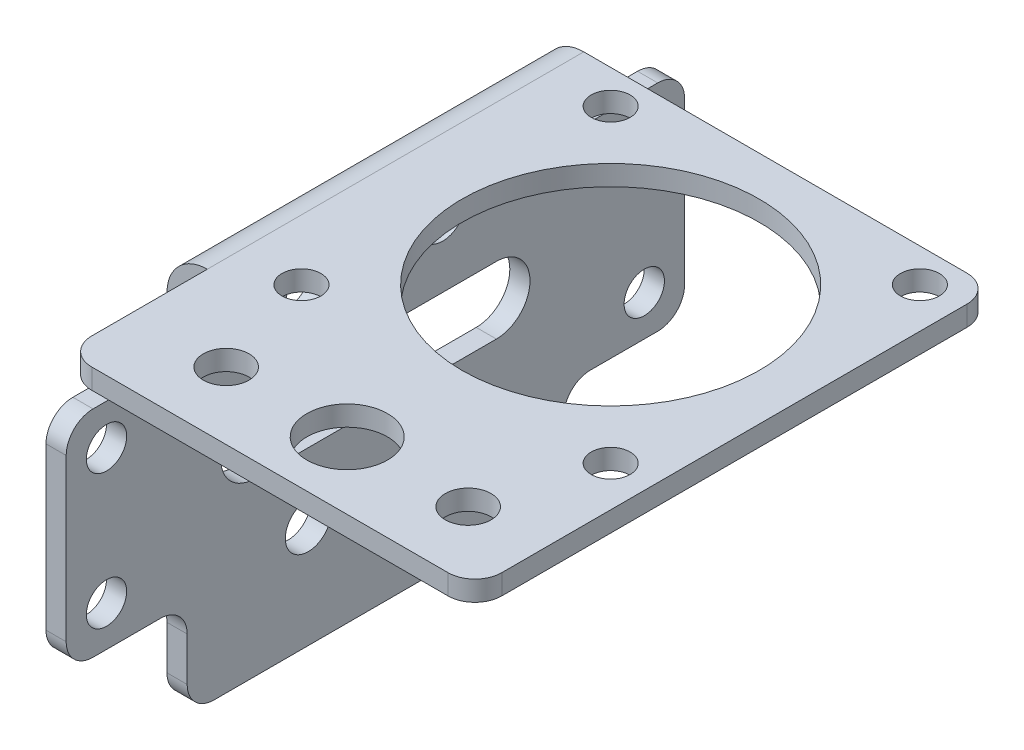
SolidWorks part; units mm, degrees
note: The reader was unsure of these and kept them because the rebuilt part matched: bend radius of "BaseBend1".
material "Plain Carbon Steel"
ref_plane "Front Plane" through (0, 0, 0) normal (0, 0, 1) x (1, 0, 0)
ref_plane "Top Plane" through (0, 0, 0) normal (0, 1, 0) x (1, 0, 0)
ref_plane "Right Plane" through (0, 0, 0) normal (1, 0, 0) x (0, 0, -1)
sketch "Sketch1" plane through (0, 0, 0) normal (0, 0, 1) x (1, 0, 0)
  line L0 (0, -24) -> (0, 0)
  line L1 (0, 0) -> (32, 0)
  dimension "D1" = 32
  dimension "D2" = 24
base flange "Base-Flange1" sketch "Sketch1" end condition mid plane depth 28 reverse direction no thickness 1.5 reverse thickness direction yes bend radius 1.5
bend "BaseBend1" bend radius 1.5 bend angle 90 parameters "D5"=1
hole_wizard "M3 Clearance Hole1" positions "Sketch6" profile "Sketch7" hole size "M3" standard "ISO" end condition through all
sketch "Sketch6" plane through (-1.5, 0, 0) normal (-1, 0, 0) x (0, 0, 1)
  line L0 (-5, -5.25) -> (-5, -20.25) construction
  line L1 (5, -5.25) -> (5, -20.25) construction
  line L2 (5, -20.25) -> (-5, -20.25) construction
  line L4 (0, -20.25) -> (0, -24) construction
  line L5 (14, -24) -> (-14, -24) construction
  line L7 (-5, -12.75) -> (-14, -12.75) construction
  line L8 (-14, -24) -> (-14, -1.5) construction
  point P0 (-5, -5.25)
  point P2 (-5, -20.25)
  point P11 (5, -5.25)
  point P13 (5, -20.25)
  dimension "D1" = 15
  dimension "D2" = 10
sketch "Sketch7" plane through (-1.5, -5.25, -5) normal (0, 1, 0) x (0, 0, 1)
  line L0 (0, 0) -> (0, 33.5)
  line L1 (0, 33.5) -> (1.7, 33.5)
  line L2 (1.7, 33.5) -> (1.7, 0)
  line L5 (1.7, 0) -> (0, 0)
  line L11 (0, -6.35) -> (0, 107.95) construction
  dimension "Thru Hole Dia." = 3.4
  dimension "Thru Hole Depth" = 33.5
hole_wizard "M2.5 Clearance Hole1" positions "Sketch8" profile "Sketch9" hole size "M2.5" standard "ISO" end condition through all
sketch "Sketch8" plane through (0, 1.5, 0) normal (0, 1, 0) x (1, 0, 0)
  line L0 (6, -11.5) -> (29, -11.5) construction
  line L1 (29, -11.5) -> (29, 11.5) construction
  line L2 (29, 11.5) -> (6, 11.5) construction
  line L4 (29, 0) -> (32, 0) construction
  line L5 (32, -14) -> (32, 14) construction
  point P0 (29, 11.5)
  point P2 (29, -11.5)
  point P4 (6, -11.5)
  point P6 (6, 11.5)
  dimension "D1" = 23
  dimension "D2" = 3
sketch "Sketch9" plane through (29, 1.5, -11.5) normal (1, 0, 0) x (0, 0, 1)
  line L0 (0, 0) -> (0, 25.5)
  line L1 (0, 25.5) -> (1.45, 25.5)
  line L2 (1.45, 25.5) -> (1.45, 0)
  line L5 (1.45, 0) -> (0, 0)
  line L11 (0, -6.35) -> (0, 107.95) construction
  dimension "Thru Hole Dia." = 2.9
  dimension "Thru Hole Depth" = 25.5
sketch "Sketch10" plane through (0, 1.5, 0) normal (0, 1, 0) x (1, 0, 0)
  line L0 (29, 11.5) -> (29, -11.5) construction
  line L1 (6, -11.5) -> (29, -11.5) construction
  line L2 (17.5, -11.5) -> (17.5, 0) construction
  line L3 (17.5, 0) -> (29, 0) construction
  circle A0 centre (17.5, 0) radius 11.05
  dimension "D1" = 22.1
extrude "Cut-Extrude1" cut sketch "Sketch10" against normal blind 10
sketch "Sketch11" plane through (0, 1.5, 0) normal (0, 1, 0) x (1, 0, 0)
  line L2 (32, -14) -> (1.5, -14)
  line L3 (17.5, -14) -> (17.5, -24.597) construction
  line L4 (1.5, -14) -> (1.5, -24.597)
  line L7 (17.5, 0) -> (17.5, -14) construction
  line L10 (1.5, -24.597) -> (17.5, -24.597)
  line L11 (17.5, -24.597) -> (32, -24.597)
  line L12 (32, -24.597) -> (32, -14)
  line L13 (28, -24.597) -> (7, -24.597) construction
  circle A8 centre (17.5, -19.597) radius 3
  dimension "D4" = 6
extrude "Boss-Extrude1" add sketch "Sketch11" against normal blind 1.5
hole_wizard "M3 Clearance Hole2" positions "Sketch12" profile "Sketch13" hole size "M3" standard "ISO" end condition through all
sketch "Sketch12" plane through (0, 0, 0) normal (0, -1, 0) x (-1, 0, 0)
  point P0 (-26.5, -19.597)
  point P3 (-8.5, -19.597)
sketch "Sketch13" plane through (26.5, 0, 19.597) normal (1, 0, 0) x (0, 0, -1)
  line L0 (0, 0) -> (0, 1.5)
  line L1 (0, 1.5) -> (1.7, 1.5)
  line L2 (1.7, 1.5) -> (1.7, 0)
  line L5 (1.7, 0) -> (0, 0)
  line L11 (0, -6.35) -> (0, 107.95) construction
  dimension "Thru Hole Dia." = 3.4
  dimension "Thru Hole Depth" = 1.5
sketch "Sketch14" plane through (0, 0, 0) normal (1, 0, 0) x (0, 0, -1)
  line L0 (14, -4.75) -> (23, -4.75)
  line L1 (14, -24) -> (14, -1.5) construction
  line L2 (23, -4.75) -> (23, -20.75)
  line L3 (23, -20.75) -> (14, -20.75)
  line L4 (14, -20.75) -> (14, -4.75)
  line L5 (14, -9.75) -> (23, -9.75) construction
  line L6 (23, -15.75) -> (14, -15.75) construction
  line L7 (20, -9.75) -> (20, -15.75) construction
  line L8 (20, -12.75) -> (23, -12.75) construction
  line L9 (20, -7.75) -> (20, -9.75) construction
  line L10 (20, -17.75) -> (20, -15.75) construction
  line L11 (-14, -24) -> (14, -24) construction
  circle A0 centre (20, -7.75) radius 1.5
  circle A1 centre (20, -17.75) radius 1.5
  dimension "D4" = 3
  dimension "D1" = 9
  dimension "D2" = 6
  dimension "D3" = 2
  dimension "D5" = 3
  dimension "D6" = 2
  dimension "D7" = 11.25
  dimension "D8" = 16
extrude "Boss-Extrude2" add sketch "Sketch14" against normal blind 1.5
mirror "Mirror1" about plane through (0, 0, 0) normal (0, 0, 1) of "Boss-Extrude2"
sketch "Sketch15" plane through (0, 0, 0) normal (1, 0, 0) x (0, 0, -1)
  line L1 (-14, -24) -> (14, -24)
  line L2 (-14, -24) -> (-14, -28)
  line L3 (-14, -28) -> (14, -28)
  line L4 (14, -24) -> (14, -28)
  dimension "D1" = 4
extrude "Boss-Extrude3" add sketch "Sketch15" against normal blind 1.5
fillet "Fillet1" radius 2 13 edges at (-0.75, -20.75, -14) (-0.75, -4.75, -14) (-0.75, -4.75, -23) (-0.75, -20.75, -23) (-0.75, -4.75, 14) (-0.75, -20.75, 14) (-0.75, -20.75, 23) (-0.75, -4.75, 23) (-0.75, -28, 14) (-0.75, -28, -14) (1.5, 0.75, 24.597) (32, 0.75, 24.597) (32, 0.75, -14)
sketch "Sketch16" plane through (0, 0, 0) normal (1, 0, 0) x (0, 0, -1)
  line L0 (-9, -12.75) -> (9, -12.75) construction
  line L1 (-9, -10.25) -> (9, -10.25)
  line L2 (-9, -15.25) -> (9, -15.25)
  line L3 (0, 0) -> (0, -12.75) construction
  line L4 (-5, -5.25) -> (-5, -12.75) construction
  line L5 (-5, -12.75) -> (-5, -20.25) construction
  arc A0 (-9, -10.25) -> (-9, -15.25) centre (-9, -12.75) ccw
  arc A1 (9, -15.25) -> (9, -10.25) centre (9, -12.75) ccw
  point P2 (0, -12.75)
  dimension "D1" = 18
  dimension "D2" = 5
extrude "Cut-Extrude2" cut sketch "Sketch16" against normal blind 10
sketch "Bend-Lines1" [suppressed] plane through (0, 0, 0) normal (0, 1, 0) x (1, 0, 0)
sketch "Bounding-Box1" [suppressed] plane through (0, 0, 0) normal (0, 1, 0) x (1, 0, 0)
sheet metal parameters "Sheet-Metal1" thickness 1.5 parameters "D1"=1.5
flat pattern "Flat-Pattern1" [suppressed]
sketch "Bend-Lines2" plane through (0, 1.5, 0) normal (0, 1, 0) x (1, 0, 0)
  line L0 (-0.2671, -14) -> (-0.2671, 14) construction
  line L1 (-0.2671, -14) -> (-0.2671, 14) construction
sketch3d "Bounding-Box2" [suppressed]
  line L0 (30, 0, 0) -> (-20.5343, 0, 0) construction
  line L1 (30, 28, 0) -> (-20.5343, 28, 0) construction
  line L2 (30, 0, 0) -> (30, 28, 0) construction
  line L3 (-20.5343, 0, 0) -> (-20.5343, 28, 0) construction
bend of the flat pattern "Flatten-<BaseBend1>1"
sheet metal parameters "Sheet-Metal2" thickness 1.5 parameters "D1"=1.5
flat pattern "Flat-Pattern1"
sketch "Bend-Lines2" plane through (0, 1.5, 0) normal (0, 1, 0) x (1, 0, 0)
  line L0 (-0.2671, -14) -> (-0.2671, 14) construction
  line L1 (-0.2671, -14) -> (-0.2671, 14) construction
sketch3d "Bounding-Box2" [suppressed]
  line L0 (30, 0, 0) -> (-20.5343, 0, 0) construction
  line L1 (30, 28, 0) -> (-20.5343, 28, 0) construction
  line L2 (30, 0, 0) -> (30, 28, 0) construction
  line L3 (-20.5343, 0, 0) -> (-20.5343, 28, 0) construction
bend of the flat pattern "Flatten-<BaseBend1>1"
sheet metal parameters "Sheet-Metal3" thickness 1.5 parameters "D1"=1.5
flat pattern "Flat-Pattern1"
sketch "Bend-Lines2" plane through (0, 1.5, 0) normal (0, 1, 0) x (1, 0, 0)
  line L0 (-0.2671, -14) -> (-0.2671, 14) construction
  line L1 (-0.2671, -14) -> (-0.2671, 14) construction
sketch3d "Bounding-Box2" [suppressed]
  line L0 (32, 0, 0) -> (-20.5343, 0, 0) construction
  line L1 (32, 28, 0) -> (-20.5343, 28, 0) construction
  line L2 (32, 0, 0) -> (32, 28, 0) construction
  line L3 (-20.5343, 0, 0) -> (-20.5343, 28, 0) construction
bend of the flat pattern "Flatten-<BaseBend1>1"
sheet metal parameters "Sheet-Metal4" thickness 1.5 parameters "D1"=1.5
flat pattern "Flat-Pattern1"
sketch "Bend-Lines2" plane through (0, 1.5, 0) normal (0, 1, 0) x (1, 0, 0)
  line L0 (-0.2671, -14) -> (-0.2671, 14) construction
  line L1 (-0.2671, -14) -> (-0.2671, 14) construction
sketch3d "Bounding-Box2" [suppressed]
  line L0 (32, 0, 0) -> (-24.5343, 0, 0) construction
  line L1 (32, 28, 0) -> (-24.5343, 28, 0) construction
  line L2 (32, 0, 0) -> (32, 28, 0) construction
  line L3 (-24.5343, 0, 0) -> (-24.5343, 28, 0) construction
bend of the flat pattern "Flatten-<BaseBend1>1"
sheet metal parameters "Sheet-Metal5" thickness 1.5 parameters "D1"=1.5
flat pattern "Flat-Pattern1"
sketch "Bend-Lines2" plane through (0, 1.5, 0) normal (0, 1, 0) x (1, 0, 0)
  line L0 (-0.2671, -14) -> (-0.2671, 14) construction
  line L1 (-0.2671, -14) -> (-0.2671, 14) construction
sketch3d "Bounding-Box2" [suppressed]
  line L0 (32, 28, 0) -> (32, -28.7409, 0) construction
  line L1 (-24.5343, 28, 0) -> (-24.5343, -28.7409, 0) construction
  line L2 (32, 28, 0) -> (-24.5343, 28, 0) construction
  line L3 (32, -28.7409, 0) -> (-24.5343, -28.7409, 0) construction
bend of the flat pattern "Flatten-<BaseBend1>1"
sheet metal parameters "Sheet-Metal7" thickness 1.5 parameters "D1"=1.5
flat pattern "Flat-Pattern1"
sketch "Bend-Lines2" plane through (0, 1.5, 0) normal (0, 1, 0) x (1, 0, 0)
  line L0 (-0.2671, -14) -> (-0.2671, 14) construction
  line L1 (-0.2671, -14) -> (-0.2671, 14) construction
sketch3d "Bounding-Box2" [suppressed]
  line L0 (32, 0, 0) -> (-24.5343, 0, 0) construction
  line L1 (32, 28, 0) -> (-24.5343, 28, 0) construction
  line L2 (32, 0, 0) -> (32, 28, 0) construction
  line L3 (-24.5343, 0, 0) -> (-24.5343, 28, 0) construction
bend of the flat pattern "Flatten-<BaseBend1>1"
sheet metal parameters "Sheet-Metal8" thickness 1.5 parameters "D1"=1.5
flat pattern "Flat-Pattern1"
sketch "Bend-Lines2" plane through (0, 1.5, 0) normal (0, 1, 0) x (1, 0, 0)
  line L0 (-0.2671, -14) -> (-0.2671, 14) construction
  line L1 (-0.2671, -14) -> (-0.2671, 14) construction
sketch3d "Bounding-Box2" [suppressed]
  line L0 (32, -10.597, 0) -> (-24.5343, -10.597, 0) construction
  line L1 (32, 28, 0) -> (-24.5343, 28, 0) construction
  line L2 (32, -10.597, 0) -> (32, 28, 0) construction
  line L3 (-24.5343, -10.597, 0) -> (-24.5343, 28, 0) construction
bend of the flat pattern "Flatten-<BaseBend1>1"
sheet metal parameters "Sheet-Metal9" thickness 1.5 parameters "D1"=1.5
flat pattern "Flat-Pattern1"
sketch "Bend-Lines2" plane through (0, 1.5, 0) normal (0, 1, 0) x (1, 0, 0)
  line L0 (-0.2671, -14) -> (-0.2671, 14) construction
  line L1 (-0.2671, -14) -> (-0.2671, 14) construction
sketch3d "Bounding-Box2" [suppressed]
  line L0 (32, -10.597, 0) -> (-24.5343, -10.597, 0) construction
  line L1 (32, 36, 0) -> (-24.5343, 36, 0) construction
  line L2 (32, -10.597, 0) -> (32, 36, 0) construction
  line L3 (-24.5343, -10.597, 0) -> (-24.5343, 36, 0) construction
bend of the flat pattern "Flatten-<BaseBend1>1"
sheet metal parameters "Sheet-Metal10" thickness 1.5 parameters "D1"=1.5
flat pattern "Flat-Pattern1"
sketch "Bend-Lines2" plane through (0, 1.5, 0) normal (0, 1, 0) x (1, 0, 0)
  line L0 (-0.2671, -14) -> (-0.2671, 14) construction
  line L1 (-0.2671, -14) -> (-0.2671, 14) construction
sketch3d "Bounding-Box2" [suppressed]
  line L0 (32, -10.597, 0) -> (-24.5343, -10.597, 0) construction
  line L1 (32, 36, 0) -> (-24.5343, 36, 0) construction
  line L2 (32, -10.597, 0) -> (32, 36, 0) construction
  line L3 (-24.5343, -10.597, 0) -> (-24.5343, 36, 0) construction
bend of the flat pattern "Flatten-<BaseBend1>1"
sheet metal parameters "Sheet-Metal11" thickness 1.5 parameters "D1"=1.5
flat pattern "Flat-Pattern1"
sketch "Bend-Lines2" plane through (0, 1.5, 0) normal (0, 1, 0) x (1, 0, 0)
  line L0 (-0.2671, -14) -> (-0.2671, 14) construction
  line L1 (-0.2671, -14) -> (-0.2671, 14) construction
sketch3d "Bounding-Box2" [suppressed]
  line L0 (-28.5343, -10.597, 0) -> (32, -10.597, 0) construction
  line L1 (-28.5343, 37, 0) -> (32, 37, 0) construction
  line L2 (-28.5343, -10.597, 0) -> (-28.5343, 37, 0) construction
  line L3 (32, -10.597, 0) -> (32, 37, 0) construction
bend of the flat pattern "Flatten-<BaseBend1>1"
sheet metal parameters "Sheet-Metal12" thickness 1.5 parameters "D1"=1.5
flat pattern "Flat-Pattern1"
sketch "Bend-Lines2" plane through (0, 1.5, 0) normal (0, 1, 0) x (1, 0, 0)
  line L0 (-0.2671, -14) -> (-0.2671, 14) construction
  line L1 (-0.2671, -14) -> (-0.2671, 14) construction
sketch3d "Bounding-Box2" [suppressed]
  line L0 (-28.5343, -10.597, 0) -> (32, -10.597, 0) construction
  line L1 (-28.5343, 37, 0) -> (32, 37, 0) construction
  line L2 (-28.5343, -10.597, 0) -> (-28.5343, 37, 0) construction
  line L3 (32, -10.597, 0) -> (32, 37, 0) construction
bend of the flat pattern "Flatten-<BaseBend1>1"
